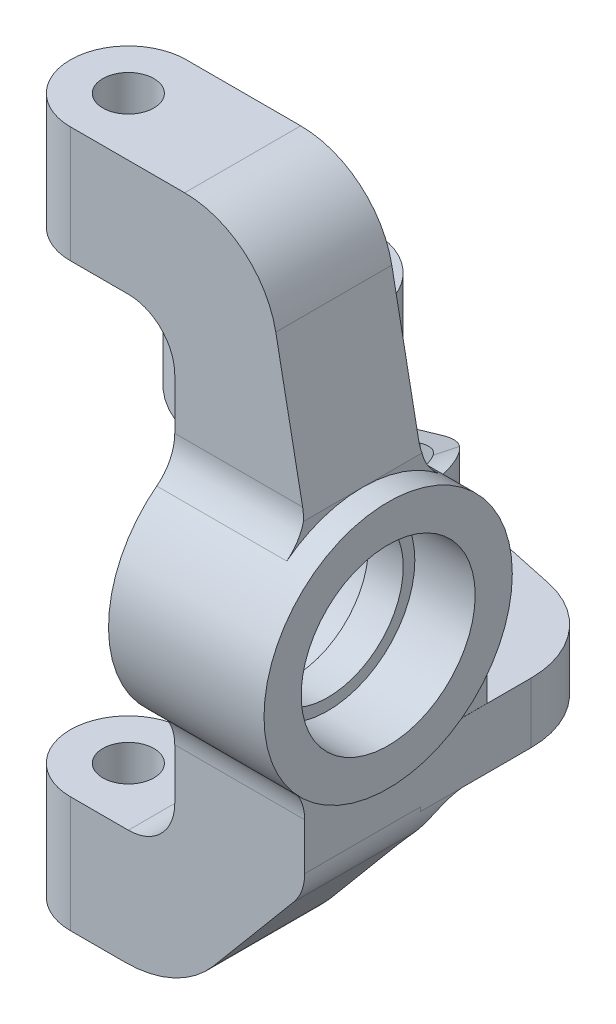
SolidWorks part; units mm, degrees
ref_plane "Front Plane" through (0, 0, 0) normal (0, 0, 1) x (1, 0, 0)
ref_plane "Top Plane" through (0, 0, 0) normal (0, 1, 0) x (1, 0, 0)
ref_plane "Right Plane" through (0, 0, 0) normal (1, 0, 0) x (0, 0, -1)
sketch "Sketch1" plane through (0, 0, 0) normal (0, 1, 0) x (1, 0, 0)
  line L0 (0, 0) -> (-8.509, 0) construction
  line L1 (0, 6.7945) -> (-8.509, 6.7945)
  line L2 (-8.509, 6.7945) -> (-8.509, 4.7625)
  line L3 (-8.509, 4.7625) -> (-5.207, 4.7625)
  line L4 (-5.207, 4.7625) -> (-5.207, 4.1275)
  line L5 (-5.207, 4.1275) -> (-3.302, 4.1275)
  line L6 (-3.302, 4.1275) -> (-3.302, 4.7625)
  line L7 (-3.302, 4.7625) -> (0, 4.7625)
  line L8 (0, 4.7625) -> (0, 6.7945)
  point P7 (-27.6908, -16.751)
  point P12 (-57.0443, -18.2959)
  dimension "D1" = 13.589
  dimension "D2" = 9.525
  dimension "D3" = 8.255
  dimension "D4" = 3.302
  dimension "D5" = 3.302
  dimension "D6" = 8.509
  dimension "D7" = 6.7945
revolve "Revolve1" add sketch "Sketch1" angle 360 about L0
sketch "Sketch3" plane through (0, 0, 0) normal (0, 0, 1) x (1, 0, 0)
  line L0 (-8.5036, -10.16) -> (-8.5036, -4.7625)
  line L1 (-11.0436, 12.7) -> (-17.3936, 12.7)
  line L2 (-1.3916, 6.7945) -> (-1.3916, 4.7625)
  line L3 (-17.3936, 12.7) -> (-17.3936, 19.05)
  line L4 (-17.3936, 19.05) -> (-7.9615, 19.05)
  line L5 (0, 0) -> (-8.5036, 0) construction
  line L6 (-11.0436, -12.7) -> (-17.3936, -12.7)
  line L7 (-17.3936, -19.05) -> (-11.2262, -19.05)
  line L8 (-17.3936, -12.7) -> (-17.3936, -19.05)
  line L9 (-1.9859, -11.5667) -> (-6.3618, -16.7817)
  line L10 (0, 6.7945) -> (-8.509, 6.7945) construction
  line L11 (-1.3916, 6.7945) -> (-2.9748, 14.9393)
  line L12 (-1.3916, 4.7625) -> (-8.5036, 4.7625)
  line L13 (-1.3916, -4.7625) -> (-8.5036, -4.7625)
  line L14 (-8.5036, 4.7625) -> (-8.5036, 10.16)
  line L15 (-1.3916, -4.7625) -> (-1.3916, -9.934)
  arc A0 (-11.2262, -19.05) -> (-6.3618, -16.7817) centre (-11.2262, -12.7) ccw
  arc A1 (-8.5036, 10.16) -> (-11.0436, 12.7) centre (-11.0436, 10.16) ccw
  arc A2 (-8.5036, -10.16) -> (-11.0436, -12.7) centre (-11.0436, -10.16) cw
  arc A3 (-2.9748, 14.9393) -> (-7.9615, 19.05) centre (-7.9615, 13.97) ccw
  arc A4 (-1.3916, -9.934) -> (-1.9859, -11.5667) centre (-3.9316, -9.934) cw
  point P22 (-8.5036, 12.7)
  point P25 (-8.5036, -12.7)
  point P29 (-1.3916, -10.8585)
  dimension "D8" = 6.35
  dimension "D9" = 2.54
  dimension "D11" = 5.08
  dimension "D12" = 2.54
  dimension "D1" = 25.4
  dimension "D2" = 7.112
  dimension "D3" = 1.3916
  dimension "D5" = 4.064
  dimension "D6" = 16.002
  dimension "D7" = 40
  dimension "D10" = 11
  dimension "D13" = 2.032
  dimension "D14" = 6.35
extrude "Boss-Extrude2" add sketch "Sketch3" along normal blind 3.175 and the other way blind 3.175
fillet "Fillet1" radius 2.54 4 edges at (-4.9476, -6.007, -3.175) (-4.9476, 6.007, -3.175) (-4.9476, 6.007, 3.175) (-4.9476, -6.007, 3.175)
fillet "Fillet2" radius 3.175 4 edges at (-17.3936, 15.875, -3.175) (-17.3936, 15.875, 3.175) (-17.3936, -15.875, -3.175) (-17.3936, -15.875, 3.175)
sketch "Sketch4" plane through (0, -19.05, 0) normal (0, -1, 0) x (1, 0, 0)
  circle A0 centre (-14.2186, 0) radius 1.397
  dimension "D1" = 2.794
extrude "Cut-Extrude1" cut sketch "Sketch4" against normal through all
ref_plane "Plane1" through (0, -10.16, 0) normal (0, 1, 0) x (-1, 0, 0)
sketch "Sketch5" plane through (0, -10.16, 0) normal (0, 1, 0) x (-1, 0, 0)
  line L0 (5.4154, -14.1903) -> (19.9638, -17.2826)
  line L1 (1.3916, -3.175) -> (1.3916, -9.2213)
  line L2 (10.3916, -10.6009) -> (25.8951, -14.7551)
  line L3 (22.9816, -22.225) -> (22.9816, -21.0094)
  line L4 (8.509, -8.1475) -> (8.509, -3.175)
  line L5 (30.6016, -22.225) -> (30.6016, -20.8887)
  line L6 (1.3916, -3.175) -> (8.509, -3.175)
  arc A0 (25.8951, -14.7551) -> (30.6016, -20.8887) centre (24.2516, -20.8887) cw
  arc A1 (19.9638, -17.2826) -> (22.9816, -21.0094) centre (19.1716, -21.0094) cw
  arc A2 (22.9816, -22.225) -> (30.6016, -22.225) centre (26.7916, -22.225) ccw
  arc A3 (8.509, -8.1475) -> (10.3916, -10.6009) centre (11.049, -8.1475) ccw
  arc A4 (1.3916, -9.2213) -> (5.4154, -14.1903) centre (6.4716, -9.2213) ccw
  circle A5 centre (26.7916, -22.225) radius 1.397
  point P14 (1.3916, -13.335)
  point P18 (8.509, -10.0965)
  point P21 (1.3916, -13.335)
  dimension "D1" = 78
  dimension "D5" = 75
  dimension "D6" = 6.35
  dimension "D8" = 3.81
  dimension "D9" = 2.54
  dimension "D10" = 3.81
  dimension "D11" = 5.08
  dimension "D12" = 2.794
  dimension "D2" = 10.16
  dimension "D3" = 25.4
  dimension "D4" = 19.05
  dimension "D7" = 4.9725
  dimension "D13" = 15.5035
extrude "Boss-Extrude3" add sketch "Sketch5" along normal blind 3.302
fillet "Fillet3" radius 2.54 1 edges at (-4.9527, -10.16, -3.175)
sketch "Sketch6" plane through (0, -6.858, 0) normal (0, 1, 0) x (1, 0, 0)
  line L0 (-30.6016, 22.225) -> (-30.6016, 20.8887) construction
  line L1 (-29.5779, 22.225) -> (-28.1848, 19.812)
  line L2 (-28.1848, 19.812) -> (-25.3985, 19.812)
  line L3 (-25.3985, 19.812) -> (-24.0053, 22.225)
  line L4 (-24.0053, 22.225) -> (-25.3985, 24.638)
  line L5 (-25.3985, 24.638) -> (-28.1848, 24.638)
  line L6 (-28.1848, 24.638) -> (-29.5779, 22.225)
  circle A0 centre (-26.7916, 22.225) radius 2.413 construction
  circle A1 centre (-26.7916, 22.225) radius 1.397 construction
  arc A2 (-22.9816, 22.225) -> (-30.6016, 22.225) centre (-26.7916, 22.225) ccw construction
  point P14 (-26.7916, 26.035)
  dimension "D1" = 4.826
  dimension "D2" = 1.0237
extrude "Cut-Extrude2" cut sketch "Sketch6" against normal blind 2.032
sketch "Sketch7" plane through (-8.509, 0, 0) normal (-1, 0, 0) x (0, 0, 1)
  line L0 (-6.7945, 0) -> (-6.7945, -6.858)
  line L1 (-8.1475, -6.858) -> (-3.175, -6.858) construction
  line L2 (-6.7945, -6.858) -> (-3.175, -6.858)
  line L7 (-3.2293, -6.858) -> (-3.175, -6.858)
  line L8 (-3.175, -6.858) -> (-3.175, -10.16)
  line L9 (-3.175, -10.16) -> (3.175, -10.16)
  line L10 (3.175, -10.16) -> (3.175, -7.3805)
  circle A0 centre (0, 0) radius 6.7945 construction
  arc A1 (-3.175, -6.858) -> (-3.5624, -6.0323) centre (-4.2488, -6.858) ccw
  arc A2 (-3.2293, -6.858) -> (-4.1599, -5.3722) centre (-5.715, -7.3805) ccw construction
  arc A3 (-4.1599, -5.3722) -> (-6.7945, 0) centre (0, 0) cw
  arc A7 (4.1599, -5.3722) -> (3.175, -7.3805) centre (5.715, -7.3805) ccw
  arc A8 (-4.1599, -5.3722) -> (4.1599, -5.3722) centre (0, 0) ccw
  arc A9 (-3.2293, -6.858) -> (-4.1599, -5.3722) centre (-5.715, -7.3805) ccw
  arc A12 (-3.5624, -6.0323) -> (-4.1599, -5.3722) centre (-5.715, -7.3805) ccw
  dimension "D2" = 6.858
  dimension "D1" = 0
extrude "Boss-Extrude4" add sketch "Sketch7" against normal blind 7.112
sketch "Sketch8" plane through (0, -6.858, 0) normal (0, 1, 0) x (1, 0, 0)
  line L0 (-21.4249, 14.8721) -> (-21.1619, 15.8535)
  line L1 (-7.239, 6.7945) -> (-6.223, 6.7945)
  line L2 (-25.5664, 15.9818) -> (-10.0629, 11.8277) construction
  line L3 (-25.3035, 16.9632) -> (-9.7999, 12.809) construction
  line L4 (-21.1619, 15.8535) -> (-9.7999, 12.809)
  line L5 (-6.223, 8.1475) -> (-6.223, 6.7945)
  line L6 (-7.239, 8.1475) -> (-7.239, 6.7945)
  line L7 (-25.5664, 15.9818) -> (-10.0629, 11.8277)
  line L8 (-7.239, 8.1475) -> (-7.239, 6.7945)
  line L9 (-21.4249, 14.8721) -> (-10.0629, 11.8277)
  arc A3 (-6.223, 8.1475) -> (-9.7999, 12.809) centre (-11.049, 8.1475) ccw
  arc A4 (-7.239, 8.1475) -> (-10.0629, 11.8277) centre (-11.049, 8.1475) ccw
  arc A5 (-7.239, 8.1475) -> (-10.0629, 11.8277) centre (-11.049, 8.1475) ccw
  dimension "D3" = 11.362
  dimension "D1" = 1.27
  dimension "D2" = 1.016
extrude "Boss-Extrude5" add sketch "Sketch8" along normal blind 7.112
chamfer "Chamfer1" distance 7.112 distance2 15.24 1 edges at (-21.2934, 0.254, -15.3628) first distance on face at (-21.2934, -3.302, -15.3628)
fillet "Fillet5" radius 6.35 1 edges at (-7.0557, 0.254, -9.6158)
